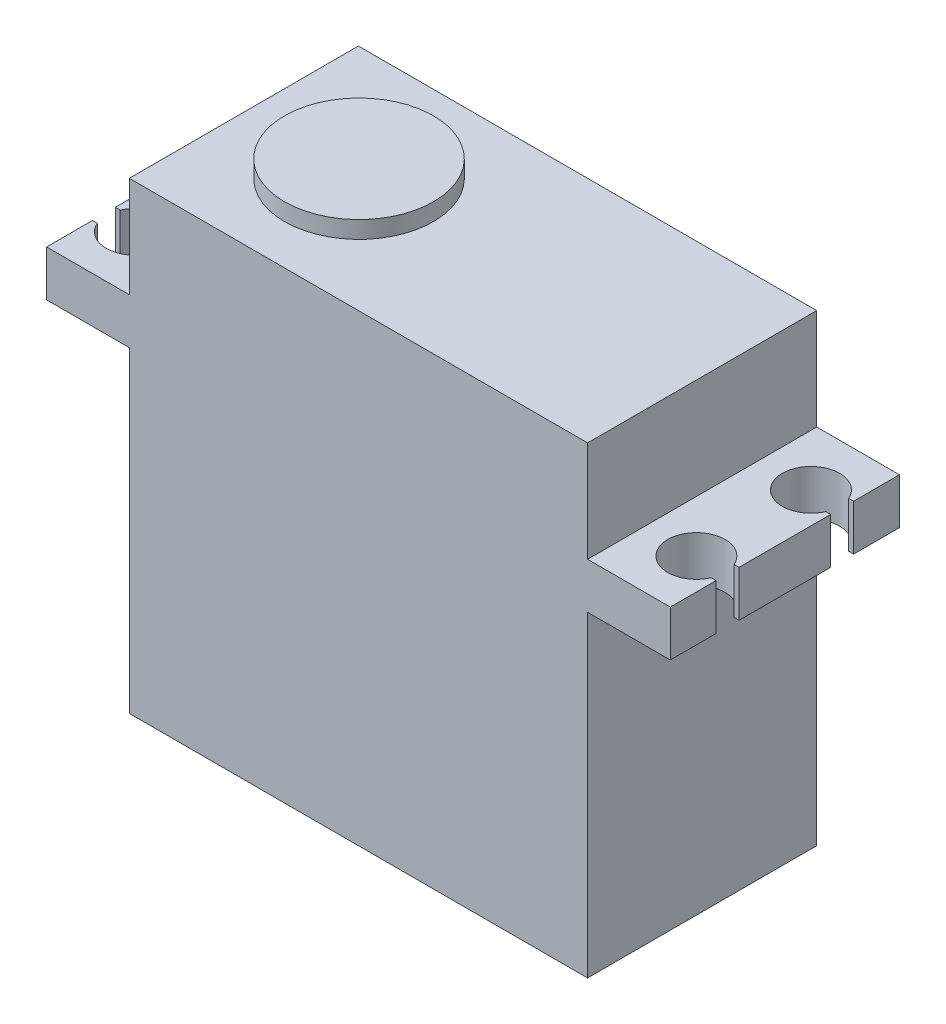
SolidWorks part; units mm, degrees
ref_plane "Front Plane" through (0, 0, 0) normal (0, 0, 1) x (1, 0, 0)
ref_plane "Top Plane" through (0, 0, 0) normal (0, 1, 0) x (1, 0, 0)
ref_plane "Right Plane" through (0, 0, 0) normal (1, 0, 0) x (0, 0, -1)
sketch "Sketch2" plane through (0, 0, 0) normal (0, 1, 0) x (1, 0, 0)
  line L1 (-20, -10) -> (20, -10)
  line L2 (-20, -10) -> (-20, 10)
  line L3 (-20, 10) -> (20, 10)
  line L4 (20, -10) -> (20, 10)
  line L5 (-20, -10) -> (20, 10) construction
  line L6 (-20, 10) -> (20, -10) construction
  point P0 (0, 0)
extrude "Boss-Extrude1" add sketch "Sketch2" along normal blind 27.65
sketch "Sketch3" plane through (-20, 0, 0) normal (-1, 0, 0) x (0, 0, 1)
  line L0 (0, 0) -> (0, 4) construction
  line L1 (-10, 0) -> (10, 0) construction
  line L3 (-3.5, 8) -> (3.5, 8)
  line L4 (-3.5, 8) -> (-3.5, 4)
  line L5 (-3.5, 4) -> (3.5, 4)
  line L6 (3.5, 8) -> (3.5, 4)
  line L7 (-3.5, 8) -> (3.5, 4) construction
  line L8 (-3.5, 4) -> (3.5, 8) construction
  point P4 (0, 6)
extrude "Boss-Extrude2" add sketch "Sketch3" along normal blind 5
sketch "Sketch5" plane through (0, 27.65, 0) normal (0, 1, 0) x (1, 0, 0)
  line L4 (20, -10) -> (20, 10)
  line L5 (20, 10) -> (-20, 10)
  line L6 (-20, 10) -> (-20, -10)
  line L7 (-20, -10) -> (20, -10)
  line L8 (20, -10) -> (20, 10)
  line L9 (20, 10) -> (-20, 10)
  line L10 (-20, 10) -> (-20, -10)
  line L11 (-20, -10) -> (20, -10)
  dimension "D1" = 0
extrude "Boss-Extrude5" add sketch "Sketch5" along normal blind 12.8
sketch "Sketch7" plane through (-20, 0, 0) normal (-1, 0, 0) x (0, 0, 1)
  line L0 (-10, 27.65) -> (10, 27.65)
  line L1 (10, 27.65) -> (10, 31.65)
  line L2 (10, 40.45) -> (10, 0) construction
  line L3 (-10, 31.65) -> (-10, 27.65)
  line L4 (-10, 40.45) -> (-10, 0) construction
  line L5 (10, 31.65) -> (-10, 31.65)
extrude "Boss-Extrude6" add sketch "Sketch7" along normal blind 7.22
sketch "Sketch8" plane through (0, 31.65, 0) normal (0, 1, 0) x (1, 0, 0)
  line L0 (-20, 10) -> (-20, 0) construction
  line L1 (-20, 0) -> (-27.22, 0) construction
  line L2 (-27.22, -10) -> (-27.22, 10) construction
  line L3 (-20, 5) -> (-22, 5) construction
  line L4 (-22, 5) -> (-27.22, 5) construction
  line L5 (-27.22, 4) -> (-27.22, 6)
  line L6 (-27.22, 6) -> (-26.7913, 6)
  line L7 (-27.22, 4) -> (-26.7913, 4)
  arc A0 (-26.7913, 4) -> (-26.7913, 6) centre (-24.5, 5) ccw
  point P14 (-27.22, 5)
extrude "Cut-Extrude3" cut sketch "Sketch8" against normal blind 4
mirror "Mirror10" about plane through (0, 0, 0) normal (0, 0, 1) of "Cut-Extrude3"
mirror "Mirror11" about plane through (0, 0, 0) normal (1, 0, 0) of "Mirror10", "Cut-Extrude3", "Boss-Extrude6"
sketch "Sketch9" plane through (0, 40.45, 0) normal (0, 1, 0) x (1, 0, 0)
  line L0 (20, 0) -> (-20, 0) construction
  line L1 (20, -10) -> (20, 10) construction
  line L2 (-20, 10) -> (-20, -10) construction
  line L5 (-9.95, 0) -> (-9.95, 8.0914) construction
  circle A1 centre (-9.95, 0) radius 6.5
  circle A2 centre (-9.95, 0) radius 3
  dimension "D2" = 29.95
extrude "Boss-Extrude8" add sketch "Sketch9" along normal blind 1.5 contours A1 A2 | A2 region at (-16.2662, 40.45, 0)
